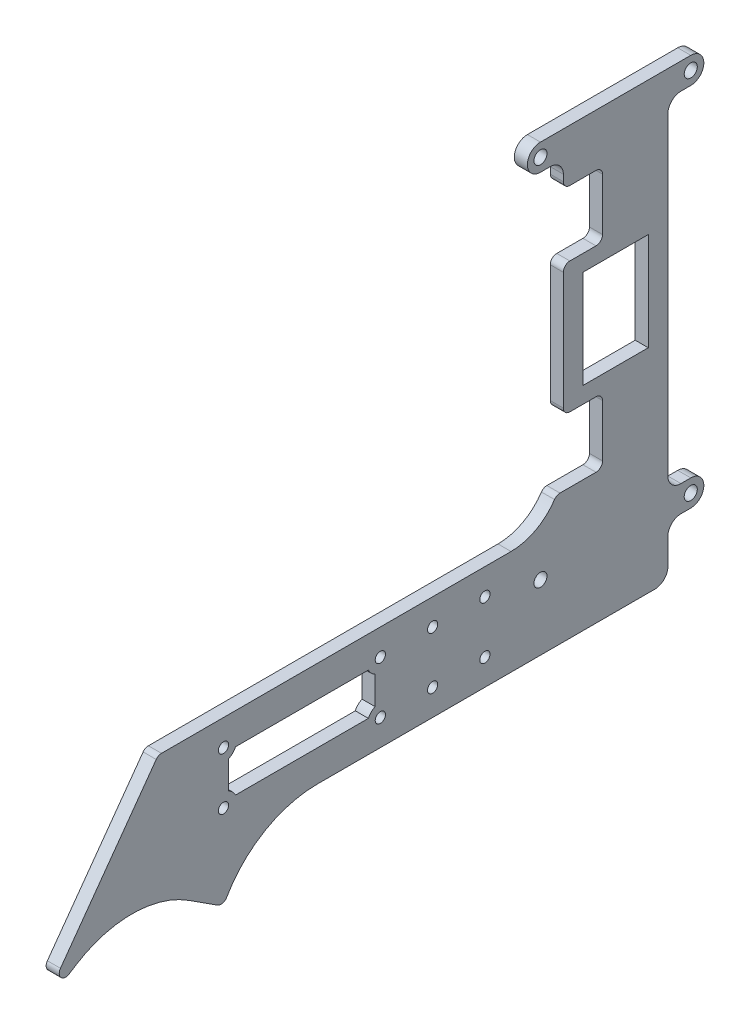
SolidWorks part; units mm, degrees
material "6061-T6 (SS)"
ref_plane "Front Plane" through (0, 0, 0) normal (0, 0, 1) x (1, 0, 0)
ref_plane "Top Plane" through (0, 0, 0) normal (0, 1, 0) x (1, 0, 0)
ref_plane "Right Plane" through (0, 0, 0) normal (1, 0, 0) x (0, 0, -1)
ref_plane "Plane1" through (228.6, 0, 0) normal (1, 0, 0) x (0, 0, -1)
sketch "Sketch1" plane through (228.6, 0, 0) normal (1, 0, 0) x (0, 0, -1)
  line L0 (179.3875, 133.35) -> (252.4125, 133.35) construction
  line L1 (241.3, 25.4) -> (241.3, 1422.4) construction
  line L2 (190.5, 25.4) -> (190.5, 1422.4) construction
  line L3 (215.9, 133.35) -> (215.9, 311.15) construction
  line L5 (252.4125, 311.15) -> (179.3875, 311.15) construction
  circle A0 centre (179.3875, 133.35) radius 11.1125
  circle A1 centre (252.4125, 133.35) radius 11.1125
  circle A2 centre (179.3875, 311.15) radius 11.1125
  circle A3 centre (252.4125, 311.15) radius 11.1125
  point P14 (215.9, 311.15)
  dimension "D1" = 22.225
  dimension "D2" = 177.8
  dimension "D3" = 6.35
sketch "Sketch2" plane through (228.6, 0, 0) normal (1, 0, 0) x (0, 0, -1)
  line L0 (-190.5, 152.4) -> (190.5, 152.4) construction
  line L1 (12.7, 152.4) -> (241.3, 152.4)
  line L2 (12.7, 152.4) -> (12.7, 101.6)
  line L3 (12.7, 101.6) -> (241.3, 101.6)
  line L4 (241.3, 152.4) -> (241.3, 101.6)
  line L5 (252.4125, 139.7) -> (241.3, 139.7)
  line L6 (190.5, 152.4) -> (241.3, 152.4)
  line L7 (190.5, 152.4) -> (190.5, 317.5)
  line L8 (190.5, 317.5) -> (241.3, 317.5)
  line L9 (241.3, 152.4) -> (241.3, 317.5)
  line L10 (252.4125, 127) -> (241.3, 127)
  line L11 (179.3875, 317.5) -> (190.5, 317.5)
  line L12 (179.3875, 304.8) -> (190.5, 304.8)
  line L13 (252.4125, 317.5) -> (241.3, 317.5)
  line L14 (252.4125, 304.8) -> (241.3, 304.8)
  line L15 (241.3, 25.4) -> (241.3, 1422.4) construction
  circle A0 centre (179.3875, 311.15) radius 6.35
  circle A1 centre (252.4125, 311.15) radius 6.35
  circle A2 centre (252.4125, 133.35) radius 6.35
  circle A3 centre (179.3875, 311.15) radius 3.175
  circle A4 centre (252.4125, 311.15) radius 3.175
  circle A5 centre (252.4125, 133.35) radius 3.175
  circle A18 centre (179.3875, 133.35) radius 3.175
  circle A19 centre (152.4, 139.7) radius 2.4892 construction
  circle A20 centre (152.4, 114.3) radius 2.4892 construction
  circle A21 centre (127, 114.3) radius 2.4892 construction
  circle A22 centre (127, 139.7) radius 2.4892 construction
  circle A23 centre (101.6, 139.7) radius 2.4892 construction
  circle A24 centre (101.6, 114.3) radius 2.4892 construction
  circle A25 centre (25.4, 114.3) radius 2.4892 construction
  circle A26 centre (25.4, 139.7) radius 2.4892 construction
  circle A27 centre (152.4, 139.7) radius 2.4892
  circle A28 centre (152.4, 114.3) radius 2.4892
  circle A29 centre (127, 114.3) radius 2.4892
  circle A30 centre (127, 139.7) radius 2.4892
  circle A31 centre (101.6, 139.7) radius 2.4892
  circle A32 centre (101.6, 114.3) radius 2.4892
  circle A33 centre (25.4, 114.3) radius 2.4892
  circle A34 centre (25.4, 139.7) radius 2.4892
  dimension "D4" = 12.7
  dimension "D5" = 6.35
  dimension "D1" = 228.6
  dimension "D2" = 50.8
extrude "Boss-Extrude1" add sketch "Sketch2" against normal blind 6.35 contours L4 L1 L2 L3 A18 A29 A28 A27 | L1 L9 L8 L7 | A0 L12 L7 L11 | A0 A3 | A1 A4 | A1 L13 L9 L14 | A2 L5 L4 L10 | A2 A5 region at (228.6, 126.9824, -127.201) region at (228.6, 234.95, -215.9) region at (228.6, 311.15, -187.2734) region at (228.6, 133.35, -244.5266) region at (228.6, 311.15, -244.5266) region at (228.6, 311.15, -173.2171) region at (228.6, 137.7131, -256.7756) region at (228.6, 311.15, -246.2421)
fillet "Fillet1" radius 25.4 1 edges at (225.425, 152.4, -190.5)
fillet "Fillet2" radius 6.35 5 edges at (225.425, 101.6, -241.3) (225.425, 139.7, -241.3) (225.425, 127, -241.3) (225.425, 304.8, -241.3) (225.425, 304.8, -190.5)
fillet "Fillet3" radius 12.7 2 edges at (225.425, 101.6, -12.7) (225.425, 152.4, -12.7)
sketch "Sketch3" plane through (228.6, 0, 0) normal (1, 0, 0) x (0, 0, -1)
  line L0 (190.5, 260.35) -> (209.55, 260.35) construction
  line L1 (209.55, 292.1) -> (209.55, 260.35) construction
  line L2 (190.5, 292.1) -> (209.55, 292.1) construction
  line L3 (190.5, 292.1) -> (190.5, 260.35) construction
  line L4 (190.5, 165.1) -> (209.55, 165.1) construction
  line L5 (209.55, 196.85) -> (209.55, 165.1) construction
  line L6 (190.5, 196.85) -> (209.55, 196.85) construction
  line L7 (190.5, 196.85) -> (190.5, 165.1) construction
  line L8 (190.5, 260.35) -> (209.55, 260.35)
  line L9 (209.55, 292.1) -> (209.55, 260.35)
  line L10 (190.5, 292.1) -> (209.55, 292.1)
  line L11 (190.5, 292.1) -> (190.5, 260.35)
  line L12 (190.5, 165.1) -> (209.55, 165.1)
  line L13 (209.55, 196.85) -> (209.55, 165.1)
  line L14 (190.5, 196.85) -> (209.55, 196.85)
  line L15 (190.5, 196.85) -> (190.5, 165.1)
  line L17 (190.5, 165.1) -> (98.0237, 165.1)
  line L18 (190.5, 165.1) -> (190.5, 190.1828)
  line L19 (190.5, 190.1828) -> (98.0237, 190.1828)
  line L20 (98.0237, 165.1) -> (98.0237, 190.1828)
  line M28 (190.5, 298.45) -> (190.5, 177.8)
  arc M29 (190.5, 177.8) -> (165.1, 152.4) centre (165.1, 177.8) cw
extrude "Cut-Extrude1" cut sketch "Sketch3" against normal through all contours L20 L17 L19 M29 M28 | L10 L8 L9 M28 | L17 L15 M29 | L15 L12 L13 L14 M28 region at (228.6, 276.225, -200.025) region at (228.6, 180.975, -200.025) region at (228.6, 177.6985, -143.9873) region at (228.6, 168.2309, -189.492)
fillet "Fillet4" radius 3.175 8 edges at (225.425, 292.1, -209.55) (225.425, 292.1, -190.5) (225.425, 260.35, -190.5) (225.425, 260.35, -209.55) (225.425, 196.85, -190.5) (225.425, 196.85, -209.55) (225.425, 165.1, -209.55) (225.425, 165.1, -187.097)
sketch "Sketch4" plane through (228.6, 0, 0) normal (1, 0, 0) x (0, 0, -1)
  line L1 (-63.5, 73.025) -> (-19.05, 101.6)
  line L2 (-19.05, 101.6) -> (25.4, 73.025)
  line L3 (-63.5, 73.025) -> (25.4, 73.025)
  line L4 (25.4, 101.6) -> (234.95, 101.6) construction
  line L5 (-63.5, 73.025) -> (-6.35, 152.4)
  line L6 (-6.35, 152.4) -> (31.2324, 152.4)
  line L7 (25.4, 152.4) -> (165.1, 152.4) construction
  line L8 (25.4, 101.6) -> (25.4, 73.025)
  arc M38 (25.4, 152.4) -> (12.7, 139.7) centre (25.4, 139.7) ccw
  line M39 (12.7, 139.7) -> (12.7, 114.3)
  arc M40 (12.7, 114.3) -> (25.4, 101.6) centre (25.4, 114.3) ccw
  dimension "D1" = 28.575
  dimension "D2" = 88.9
  dimension "D3" = 57.15
extrude "Boss-Extrude2" add sketch "Sketch4" against normal blind 6.35 contours L8 L6 L5 L1 L2 M40 M39 M38 region at (228.6, 112.7386, 7.0099)
fillet "Fillet5" radius 50.8 2 edges at (225.425, 101.6, 19.05) (225.425, 101.6, -25.4)
fillet "Fillet6" radius 3.1496 3 edges at (225.425, 73.025, 63.5) (225.425, 152.4, 6.35) (225.425, 73.025, -25.4)
sketch "Sketch5" plane through (228.6, 0, 0) normal (1, 0, 0) x (0, 0, -1)
  line L0 (25.4, 139.7) -> (25.4, 114.3) construction
  line L1 (25.4, 114.3) -> (101.6, 114.3) construction
  line L2 (101.6, 114.3) -> (127, 114.3) construction
  line L3 (127, 114.3) -> (152.4, 114.3) construction
  line L4 (152.4, 114.3) -> (152.4, 139.7) construction
  line L5 (152.4, 139.7) -> (127, 139.7) construction
  line L6 (127, 139.7) -> (101.6, 139.7) construction
  line L7 (101.6, 139.7) -> (25.4, 139.7) construction
  line L8 (101.6, 139.7) -> (101.6, 114.3) construction
  line L10 (200.025, 252.4125) -> (231.775, 252.4125)
  line L11 (200.025, 252.4125) -> (200.025, 204.7875)
  line L12 (200.025, 204.7875) -> (231.775, 204.7875)
  line L13 (231.775, 252.4125) -> (231.775, 204.7875)
  line L14 (200.025, 252.4125) -> (200.025, 260.35) construction
  line L15 (193.675, 260.35) -> (206.375, 260.35) construction
  line L16 (200.025, 204.7875) -> (200.025, 196.85) construction
  line L17 (193.675, 196.85) -> (206.375, 196.85) construction
  line L18 (190.5, 228.6) -> (200.025, 228.6) construction
  line L19 (190.5, 200.025) -> (190.5, 257.175) construction
  line L20 (200.025, 228.6) -> (231.775, 228.6) construction
  line L21 (231.775, 228.6) -> (241.3, 228.6) construction
  line L22 (241.3, 298.45) -> (241.3, 146.05) construction
  line L23 (99.06, 137.16) -> (27.94, 137.16)
  line L24 (27.94, 137.16) -> (27.94, 116.84)
  line L25 (27.94, 116.84) -> (99.06, 116.84)
  line L26 (99.06, 137.16) -> (99.06, 116.84)
  circle A4 centre (25.4, 139.7) radius 6.35
  circle A5 centre (101.6, 139.7) radius 6.35
  circle A6 centre (101.6, 114.3) radius 6.35
  circle A7 centre (25.4, 114.3) radius 6.35
  dimension "D4" = 12.7
  dimension "D1" = 31.75
  dimension "D2" = 47.625
  dimension "D3" = 2.54
extrude "Cut-Extrude2" cut sketch "Sketch5" against normal through all contours A7 L25 A6 L26 A5 L23 A4 L24 | L13 L10 L11 L12 region at (228.6, 228.6, -215.9) region at (228.6, 127, -63.5)
